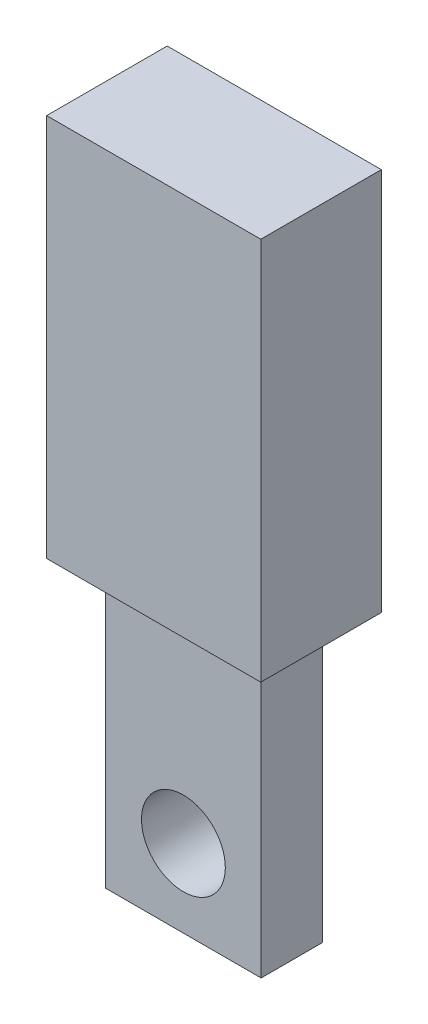
SolidWorks part; units mm, degrees
ref_plane "Front Plane" through (0, 0, 0) normal (0, 0, 1) x (1, 0, 0)
ref_plane "Top Plane" through (0, 0, 0) normal (0, 1, 0) x (1, 0, 0)
ref_plane "Right Plane" through (0, 0, 0) normal (1, 0, 0) x (0, 0, -1)
sketch "Sketch1" plane through (0, 0, 0) normal (0, 1, 0) x (1, 0, 0)
  line L1 (-32.258, 12.7) -> (32.258, 12.7)
  line L2 (-32.258, 12.7) -> (-32.258, -12.7)
  line L3 (-32.258, -12.7) -> (32.258, -12.7)
  line L4 (32.258, 12.7) -> (32.258, -12.7)
  dimension "D1" = 64.516
extrude "Extrude2" add sketch "Sketch1" along normal blind 59.309 and the other way blind 59.309
sketch "Sketch2" plane through (0, 0, 0) normal (0, 0, 1) x (1, 0, 0)
  line L0 (-32.258, -59.309) -> (32.258, -59.309) construction
  circle A0 centre (0, -27.051) radius 17.399
  dimension "D2" = 34.798
  dimension "D1" = 32.258
extrude "Cut-Extrude1" cut sketch "Sketch2" against normal through all and the other way through all
ref_plane "Plane1" through (0, 59.309, 0) normal (0, 1, 0) x (-1, 0, 0)
sketch "Sketch3" plane through (0, 59.309, 0) normal (0, 1, 0) x (-1, 0, 0)
  line L1 (-44.45, 25.019) -> (44.45, 25.019)
  line L2 (-44.45, 25.019) -> (-44.45, -25.019)
  line L3 (-44.45, -25.019) -> (44.45, -25.019)
  line L4 (44.45, 25.019) -> (44.45, -25.019)
  dimension "D1" = 88.9
extrude "Extrude3" add sketch "Sketch3" along normal blind 159.258
sketch "Sketch4" plane through (0, 0, 0) normal (0, 0, 1) x (1, 0, 0)
  line L0 (0, 0) -> (0, 14.3789)
